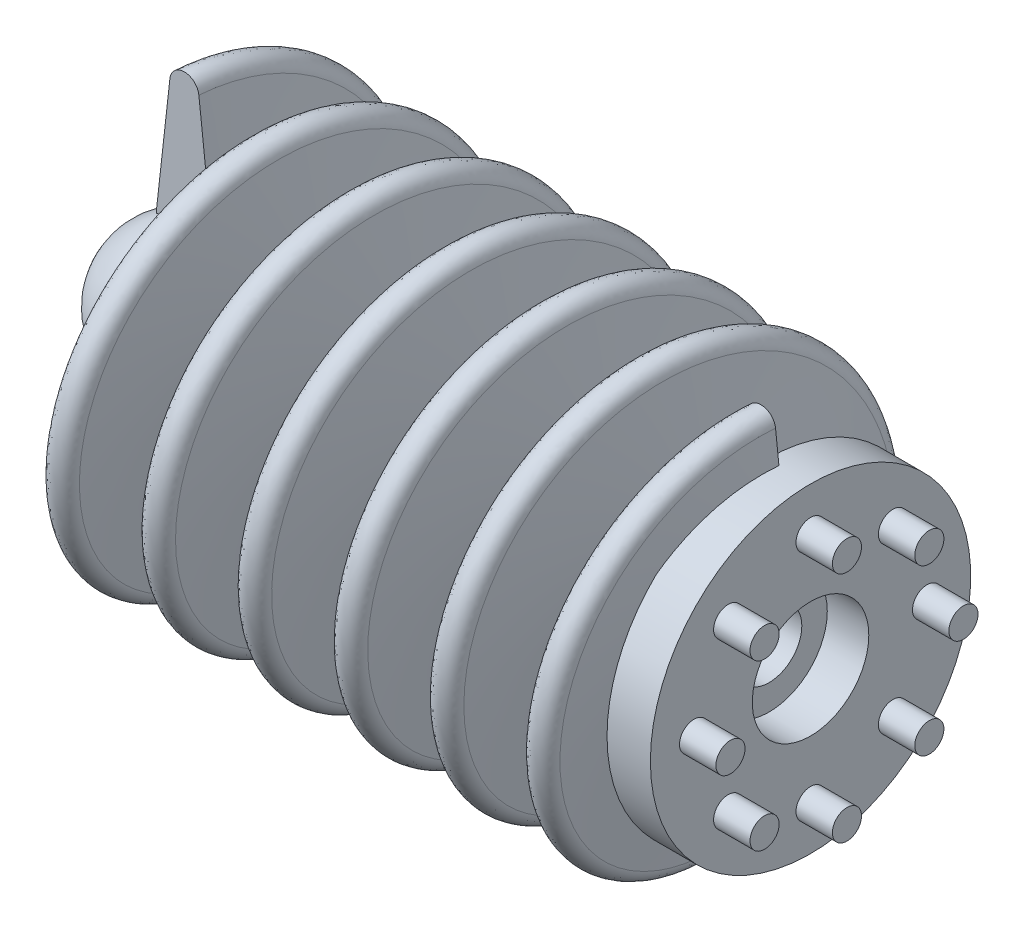
SolidWorks part; units mm, degrees
ref_plane "Front Plane" through (0, 0, 0) normal (0, 0, 1) x (1, 0, 0)
ref_plane "Top Plane" through (0, 0, 0) normal (0, 1, 0) x (1, 0, 0)
ref_plane "Right Plane" through (0, 0, 0) normal (1, 0, 0) x (0, 0, -1)
sketch "Sketch2" plane through (0, 0, 0) normal (0, 0, 1) x (1, 0, 0)
  line L0 (-35.4233, -11.586) -> (12.5767, -11.586)
  line L1 (12.5767, -11.586) -> (12.5767, -0.586)
  line L2 (12.5767, -0.586) -> (9.6, -0.586)
  line L3 (9.6, -0.586) -> (9.6, -6.586)
  line L4 (-35.4233, -11.586) -> (-35.4233, -6.586)
  line L5 (-35.4233, -6.586) -> (9.6, -6.586)
  dimension "D1" = 48
  dimension "D2" = 11
  dimension "D3" = 5
revolve "Revolve1" add sketch "Sketch2" angle 360 about L0
sketch "Sketch3" plane through (9.6, 0, 0) normal (-1, 0, 0) x (0, 0, 1)
  circle A0 centre (0, -11.586) radius 5
curve "Helix/Spiral1" pitch 6.6 height 39.6 radius 5 left hand yes centre (9.6, -11.586, 0) axis (-1, 0, 0) start towards (0, 1, 0)
fillet "Fillet6" radius 5 1 edges at (-35.4233, -11.586, 5)
sketch "Sketch7" plane through (0, 0, 0) normal (0, 0, 1) x (1, 0, 0)
  line L0 (-30.4233, -6.586) -> (-30.4233, 1.414) construction
  line L1 (-29.4294, 1.525) -> (-28.5233, -6.586)
  line L2 (9.6, -6.586) -> (-30.4233, -6.586) construction
  line L3 (-28.5233, -6.586) -> (-28.5233, -7.286)
  line L4 (-28.5233, -7.286) -> (-30.4233, -7.286)
  line L5 (-30.4233, -16.586) -> (-30.4233, -6.586) construction
  line L6 (-30.4233, -7.286) -> (-32.3233, -7.286)
  line L7 (-32.3233, -7.286) -> (-32.3233, -6.586)
  line L8 (-32.3233, -6.586) -> (-31.4171, 1.525)
  arc A0 (-29.4294, 1.525) -> (-31.4171, 1.525) centre (-30.4233, 1.414) ccw
  dimension "D2" = 2
  dimension "D1" = 8
  dimension "D3" = 0.7
  dimension "D4" = 1.9
  dimension "D5" = 1.9
  dimension "D6" = 0.7
sketch "Sketch9" plane through (12.5767, 0, 0) normal (1, 0, 0) x (0, 0, -1)
  circle A0 centre (0, -11.586) radius 11
  circle A1 centre (0, -11.586) radius 4
  dimension "D1" = 8
extrude "Cut-Extrude1" cut sketch "Sketch9" against normal blind 2.85 contours A1
sketch "Sketch10" plane through (9.7267, 0, 0) normal (1, 0, 0) x (0, 0, -1)
  circle A0 centre (0, -11.586) radius 2.25
  dimension "D1" = 4.5
extrude "Cut-Extrude2" cut sketch "Sketch10" against normal blind 2.5
sketch "Sketch11" plane through (12.5767, 0, 0) normal (1, 0, 0) x (0, 0, -1)
  line L0 (0, -11.586) -> (0, -3.586)
  circle A0 centre (0, -3.586) radius 1
  dimension "D2" = 2
  dimension "D1" = 8
extrude "Boss-Extrude1" add sketch "Sketch11" along normal blind 2.5 contours A0
pattern_circular "CirPattern1" count 8 over 360 about axis through (-35.4233, -11.586, 0) along (-1, 0, 0) of "Boss-Extrude1"
sweep "Sweep2" add profiles "Sketch7" path "Helix/Spiral1"
